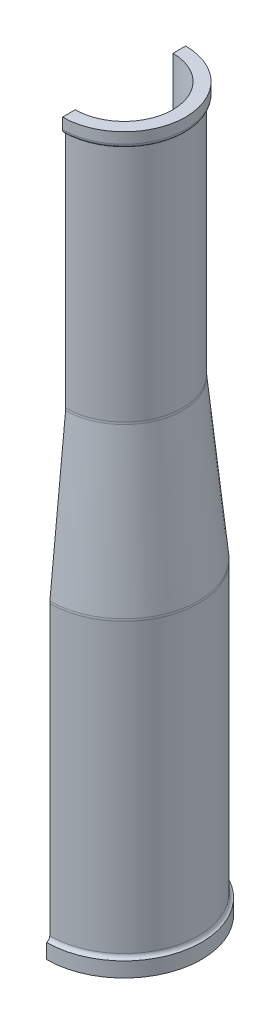
SolidWorks part; units mm, degrees
ref_plane "Alzado" through (0, 0, 0) normal (0, 0, 1) x (1, 0, 0)
ref_plane "Planta" through (0, 0, 0) normal (0, 1, 0) x (1, 0, 0)
ref_plane "Vista lateral" through (0, 0, 0) normal (1, 0, 0) x (0, 0, -1)
sketch "Croquis1" plane through (0, 0, 0) normal (0, 1, 0) x (1, 0, 0)
  circle A0 centre (0, 0) radius 35
  dimension "D1" = 70
extrude "Saliente-Extruir1" add sketch "Croquis1" along normal blind 145
ref_plane "Plano1" through (0, 220, 0) normal (0, 1, 0) x (1, 0, 0)
sketch "Croquis2" plane through (0, 220, 0) normal (0, 1, 0) x (1, 0, 0)
  circle A2 centre (0, 0) radius 27.5
  dimension "D1" = 55
loft "Recubrir1" add profiles "Croquis2" section edge at (0, 145, 35) section "Croquis2" connector at (-33.8055, 145, 9.0657) connector at (-26.1001, 220, 8.6621)
sketch "Croquis3" plane through (0, 220, 0) normal (0, 1, 0) x (1, 0, 0)
  circle A0 centre (0, 0) radius 27.5 construction
  circle A1 centre (0, 0) radius 27.5
extrude "Saliente-Extruir2" add sketch "Croquis3" along normal blind 120
sketch "Croquis5" plane through (0, 0, 0) normal (0, -1, 0) x (1, 0, 0)
  circle A0 centre (0, 0) radius 36.5
  dimension "D1" = 73
extrude "Saliente-Extruir3" add sketch "Croquis5" against normal blind 7
sketch "Croquis4" plane through (0, 0, 0) normal (0, -1, 0) x (1, 0, 0)
  circle A0 centre (0, 0) radius 23
  dimension "D1" = 46
extrude "Cortar-Extruir1" cut sketch "Croquis4" against normal blind 525
fillet "Redondeo1" radius 10 2 edges at (0, 220, 27.5) (0, 145, 35)
sketch "Croquis6" plane through (0, 340, 0) normal (0, 1, 0) x (1, 0, 0)
  circle A0 centre (0, 0) radius 29
  circle A1 centre (0, 0) radius 23 construction
  circle A2 centre (0, 0) radius 23
  dimension "D1" = 58
extrude "Saliente-Extruir4" add sketch "Croquis6" against normal blind 7
fillet "Redondeo2" radius 2 2 edges at (0, 333, 29) (0, 7, -35)
sketch "Croquis7" plane through (0, 0, 0) normal (1, 0, 0) x (0, 0, -1)
  line L1 (50.2617, 0) -> (-69.4769, 0)
  line L2 (50.2617, 0) -> (50.2617, 395.3893)
  line L3 (50.2617, 395.3893) -> (-69.4769, 395.3893)
  line L4 (-69.4769, 0) -> (-69.4769, 395.3893)
  dimension "D1" = 395.3893
  dimension "D2" = 119.7386
  dimension "D3" = 50.2617
extrude "Cortar-Extruir2" cut sketch "Croquis7" against normal blind 93
